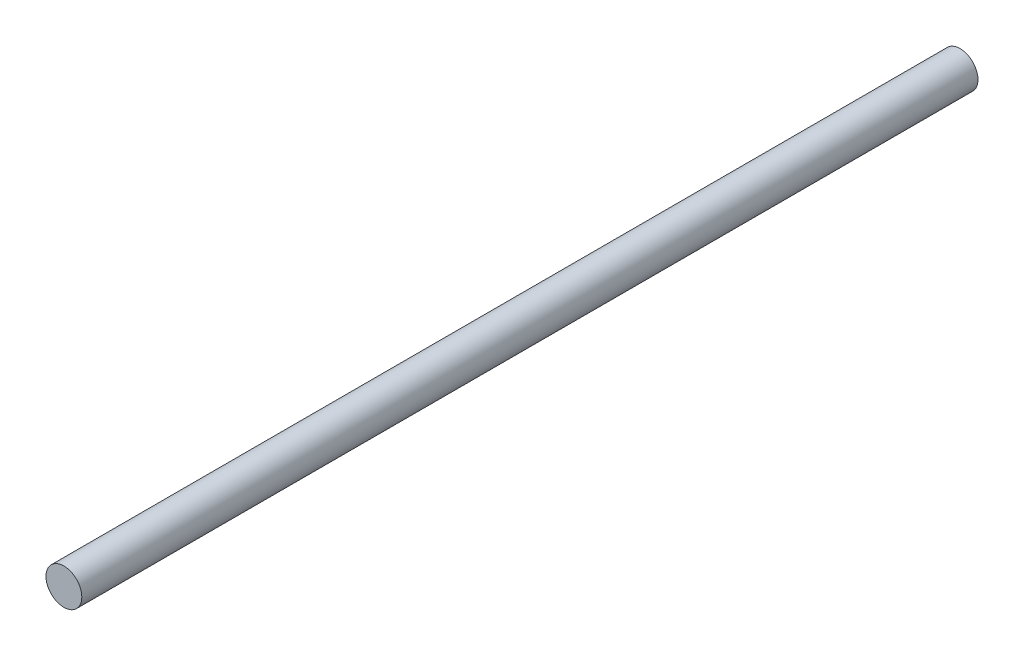
SolidWorks part; units mm, degrees
ref_plane "Front Plane" through (0, 0, 0) normal (0, 0, 1) x (1, 0, 0)
ref_plane "Top Plane" through (0, 0, 0) normal (0, 1, 0) x (1, 0, 0)
ref_plane "Right Plane" through (0, 0, 0) normal (1, 0, 0) x (0, 0, -1)
sketch "Sketch1" plane through (0, 0, 0) normal (0, 0, 1) x (1, 0, 0)
  circle A0 centre (0, 0) radius 3
  dimension "D1" = 6
extrude "Boss-Extrude1" add sketch "Sketch1" along normal mid plane 150
ref_axis "Axis1" through (0, 0, 75) along (0, 0, -1)
